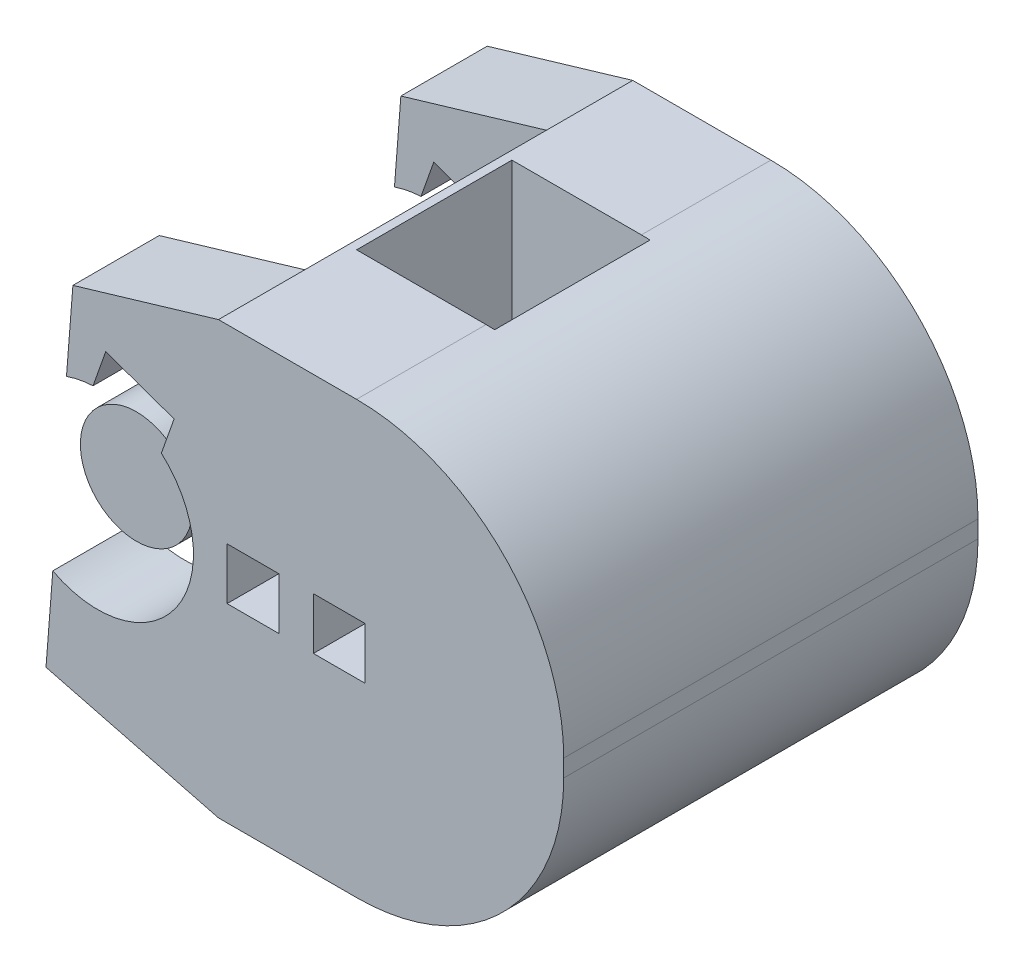
SolidWorks part; units mm, degrees
material "ABS"
ref_plane "正面" through (0, 0, 0) normal (0, 0, 1) x (1, 0, 0)
ref_plane "平面" through (0, 0, 0) normal (0, 1, 0) x (1, 0, 0)
ref_plane "右側面" through (0, 0, 0) normal (1, 0, 0) x (0, 0, -1)
sketch "ｽｹｯﾁ1" plane through (0, 0, 0) normal (0, 0, 1) x (1, 0, 0)
  circle A0 centre (0, 0) radius 3.25
  dimension "D1" = 6.5
extrude "ﾎﾞｽ - 押し出し1" add sketch "ｽｹｯﾁ1" along normal blind 19.5
ref_plane "平面1" through (5, 0, 0) normal (1, 0, 0) x (0, 0, -1)
sketch "ｽｹｯﾁ2" plane through (5, 0, 0) normal (1, 0, 0) x (0, 0, -1)
  line L0 (-19.5, 0) -> (0, 0) construction
  line L1 (-19.5, 3.25) -> (-19.5, -3.25) construction
  line L3 (-2.75, -7.5) -> (-16.75, -7.5)
  line L4 (-2.75, -7.5) -> (-2.75, 7.5)
  line L5 (-2.75, 7.5) -> (-16.75, 7.5)
  line L6 (-16.75, -7.5) -> (-16.75, 7.5)
  line L7 (-2.75, -7.5) -> (-16.75, 7.5) construction
  line L8 (-2.75, 7.5) -> (-16.75, -7.5) construction
  point P5 (-9.75, 0)
  dimension "D1" = 15
  dimension "D2" = 14
extrude "ﾎﾞｽ - 押し出し2" add sketch "ｽｹｯﾁ2" along normal blind 2 separate body
sketch "ｽｹｯﾁ3" plane through (0, 0, 2.75) normal (0, 0, -1) x (-1, 0, 0)
  line L0 (0, 0) -> (-5, 4.5)
  line L1 (-5, 3.575) -> (-5, -3.575) construction
  line L2 (-5, 4.5) -> (-5, -4.5)
  line L3 (-5, -4.5) -> (0, 0)
  dimension "D1" = 9
extrude "ﾎﾞｽ - 押し出し3" add sketch "ｽｹｯﾁ3" against normal up to surface (14 mm away) up to face at (6, 0, 16.75)
fillet "ﾌｨﾚｯﾄ1" radius 2 4 edges at (5, -4.5, 9.75) (2.4157, -2.1741, 9.75) (2.4157, 2.1741, 9.75) (5, 4.5, 9.75)
sketch "ｽｹｯﾁ5" plane through (7, 0, 0) normal (1, 0, 0) x (0, 0, -1)
  line L0 (-16.75, 0) -> (-2.75, 0) construction
  line L3 (-16.75, 7.5) -> (-16.75, -7.5) construction
  line L16 (-2.75, -2.9305) -> (-2.75, 2.9305) construction
  line L18 (-21.75, -12.5) -> (2.25, -12.5)
  line L19 (-21.75, -12.5) -> (-21.75, 12.5)
  line L20 (-21.75, 12.5) -> (2.25, 12.5)
  line L21 (2.25, -12.5) -> (2.25, 12.5)
  line L22 (-21.75, -12.5) -> (2.25, 12.5) construction
  line L23 (-21.75, 12.5) -> (2.25, -12.5) construction
  point P6 (-9.75, 0)
  dimension "D1" = 25
  dimension "D2" = 24
extrude "ﾎﾞｽ - 押し出し4" add sketch "ｽｹｯﾁ5" along normal blind 20
sketch "ｽｹｯﾁ6" plane through (27, 0, 0) normal (1, 0, 0) x (0, 0, -1)
  line L0 (-21.75, 0) -> (2.25, 0) construction
  line L1 (-21.75, 12.5) -> (-21.75, -12.5) construction
  line L2 (2.25, -12.5) -> (2.25, 12.5) construction
  line L4 (-11.75, -1.25) -> (-14.25, -1.25)
  line L5 (-11.75, -1.25) -> (-11.75, 1.25)
  line L6 (-11.75, 1.25) -> (-14.25, 1.25)
  line L7 (-14.25, -1.25) -> (-14.25, 1.25)
  line L8 (-11.75, -1.25) -> (-14.25, 1.25) construction
  line L9 (-11.75, 1.25) -> (-14.25, -1.25) construction
  line L10 (-5.25, -1.25) -> (-7.75, -1.25)
  line L11 (-5.25, -1.25) -> (-5.25, 1.25)
  line L12 (-5.25, 1.25) -> (-7.75, 1.25)
  line L13 (-7.75, -1.25) -> (-7.75, 1.25)
  line L14 (-5.25, -1.25) -> (-7.75, 1.25) construction
  line L15 (-5.25, 1.25) -> (-7.75, -1.25) construction
  point P6 (-13, 0)
  point P8 (-9.75, 0)
  point P12 (-6.5, 0)
  dimension "D1" = 3.25
  dimension "D2" = 3.25
  dimension "D3" = 2.5
  dimension "D4" = 2.5
extrude "ｶｯﾄ - 押し出し1" cut sketch "ｽｹｯﾁ6" against normal through all
sketch "ｽｹｯﾁ7" plane through (0, 0, 21.75) normal (0, 0, 1) x (1, 0, 0)
  line L0 (0, 0) -> (27, 0) construction
  line L1 (27, 12.5) -> (27, -12.5) construction
  line L2 (7, 12.5) -> (7, -12.5) construction
  line L3 (10.5, 1.5) -> (7.5, 1.5)
  line L4 (10.5, 1.5) -> (10.5, -1.5)
  line L5 (10.5, -1.5) -> (7.5, -1.5)
  line L6 (7.5, 1.5) -> (7.5, -1.5)
  line L7 (10.5, 1.5) -> (7.5, -1.5) construction
  line L8 (10.5, -1.5) -> (7.5, 1.5) construction
  line L9 (15.5, 1.5) -> (12.5, 1.5)
  line L10 (15.5, 1.5) -> (15.5, -1.5)
  line L11 (15.5, -1.5) -> (12.5, -1.5)
  line L12 (12.5, 1.5) -> (12.5, -1.5)
  line L13 (15.5, 1.5) -> (12.5, -1.5) construction
  line L14 (15.5, -1.5) -> (12.5, 1.5) construction
  point P5 (9, 0)
  point P10 (14, 0)
  dimension "D1" = 3
  dimension "D2" = 2
  dimension "D3" = 5
extrude "ｶｯﾄ - 押し出し2" cut sketch "ｽｹｯﾁ7" against normal through all
sketch "ｽｹｯﾁ8" plane through (0, 12.5, 0) normal (0, 1, 0) x (1, 0, 0)
  line L0 (3, -5.25) -> (7.5, -5.25) construction
  line L1 (7.5, -5.25) -> (15.5, -5.25)
  line L2 (7.5, -5.25) -> (7.5, -14.25)
  line L3 (7.5, -14.25) -> (15.5, -14.25)
  line L4 (15.5, -5.25) -> (15.5, -14.25)
  line L5 (-3, -14.25) -> (7.5, -14.25) construction
  line L6 (7.5, 2.25) -> (7.5, -21.75) construction
  line L7 (15.5, 2.25) -> (15.5, -5.25) construction
extrude "ｶｯﾄ - 押し出し3" cut sketch "ｽｹｯﾁ8" against normal through all
sketch "ｽｹｯﾁ9" plane through (15.5, 0, 0) normal (-1, 0, 0) x (0, 0, 1)
  line L4 (11.75, -1.25) -> (14.25, -1.25)
  line L5 (14.25, -1.25) -> (14.25, 1.25)
  line L6 (14.25, 1.25) -> (11.75, 1.25)
  line L7 (11.75, 1.25) -> (11.75, -1.25)
  line L8 (11.75, -1.25) -> (14.25, -1.25)
  line L9 (14.25, -1.25) -> (14.25, 1.25)
  line L10 (14.25, 1.25) -> (11.75, 1.25)
  line L11 (11.75, 1.25) -> (11.75, -1.25)
  line L12 (5.25, -1.25) -> (7.75, -1.25)
  line L13 (5.25, 1.25) -> (5.25, -1.25)
  line L14 (7.75, 1.25) -> (5.25, 1.25)
  line L15 (7.75, -1.25) -> (7.75, 1.25)
  line L16 (5.25, -1.25) -> (7.75, -1.25)
  line L17 (5.25, 1.25) -> (5.25, -1.25)
  line L18 (7.75, 1.25) -> (5.25, 1.25)
  line L19 (7.75, -1.25) -> (7.75, 1.25)
  dimension "D1" = 0
  dimension "D2" = 0
extrude "ﾎﾞｽ - 押し出し5" add sketch "ｽｹｯﾁ9" against normal up to surface (11.5 mm away) up to face at (27, 0, 13)
fillet "ﾌｨﾚｯﾄ7" radius 12 2 edges at (27, -12.5, 9.75) (27, 12.5, 9.75)
sketch "ｽｹｯﾁ10" plane through (0, 0, 2.75) normal (0, 0, -1) x (-1, 0, 0)
  line L3 (1.8051, 5.2483) -> (2.5982, -4.9043) construction
  line L4 (1.8051, 5.2483) -> (1.4339, 10)
  line L5 (1.4339, 10) -> (-7, 12.5)
  line L6 (-4.4294, 6.23) -> (-3.692, 4.1438)
  line L7 (-0.4695, 7.6297) -> (-4.4294, 6.23)
  line L8 (0.2679, 5.5435) -> (-0.4695, 7.6297)
  line L9 (-4.4294, 6.23) -> (-3.692, 4.1438)
  line L10 (-0.4695, 7.6297) -> (-4.4294, 6.23)
  line L11 (0.2679, 5.5435) -> (-0.4695, 7.6297)
  line L12 (2.5982, -4.9043) -> (2.9915, -9.9393)
  line L13 (2.9915, -9.9393) -> (-7, -12.5)
  line L14 (1.4339, 10) -> (-7, 10) construction
  line L15 (-7, -12.5) -> (-7, 12.5) construction
  line L16 (2.9915, -9.9393) -> (-7, -9.9393) construction
  line L17 (-7, 12.5) -> (-7, -12.5)
  arc A4 (1.8051, 5.2483) -> (0.2679, 5.5435) centre (0, 0) ccw
  arc A5 (-3.692, 4.1438) -> (2.5982, -4.9043) centre (0, 0) ccw
  arc A6 (1.8051, 5.2483) -> (0.2679, 5.5435) centre (0, 0) ccw
  arc A7 (-3.692, 4.1438) -> (2.5982, -4.9043) centre (0, 0) ccw
  point P0 (2.9652, -9.6768)
  dimension "D2" = 20
  dimension "D3" = 2.5
  dimension "D1" = 0.1
extrude "ﾎﾞｽ - 押し出し6" add sketch "ｽｹｯﾁ10" along normal up to surface (5 mm away) up to face at (9, 0, -2.25)
sketch "ｽｹｯﾁ11" plane through (0, 0, 16.75) normal (0, 0, -1) x (-1, 0, 0)
  line L8 (1.8051, 5.2483) -> (1.4339, 10)
  line L9 (1.4339, 10) -> (-7, 12.5)
  line L10 (-7, 12.5) -> (-7, -12.5)
  line L11 (-7, -12.5) -> (2.9915, -9.9393)
  line L12 (2.9915, -9.9393) -> (2.5982, -4.9043)
  line L13 (-3.692, 4.1438) -> (-4.4294, 6.23)
  line L14 (-4.4294, 6.23) -> (-0.4695, 7.6297)
  line L15 (-0.4695, 7.6297) -> (0.2679, 5.5435)
  line L16 (1.8051, 5.2483) -> (1.4339, 10)
  line L17 (1.4339, 10) -> (-7, 12.5)
  line L18 (-7, 12.5) -> (-7, -12.5)
  line L19 (-7, -12.5) -> (2.9915, -9.9393)
  line L20 (2.9915, -9.9393) -> (2.5982, -4.9043)
  line L21 (-3.692, 4.1438) -> (-4.4294, 6.23)
  line L22 (-4.4294, 6.23) -> (-0.4695, 7.6297)
  line L23 (-0.4695, 7.6297) -> (0.2679, 5.5435)
  arc A2 (-3.692, 4.1438) -> (2.5982, -4.9043) centre (0, 0) ccw
  arc A3 (1.8051, 5.2483) -> (0.2679, 5.5435) centre (0, 0) ccw
  arc A4 (-3.692, 4.1438) -> (2.5982, -4.9043) centre (0, 0) ccw
  arc A5 (1.8051, 5.2483) -> (0.2679, 5.5435) centre (0, 0) ccw
  dimension "D1" = 0
extrude "ﾎﾞｽ - 押し出し7" add sketch "ｽｹｯﾁ11" against normal up to surface (5 mm away) up to face at (9, 0, 21.75)
equation "\"D2@ｽｹｯﾁ6\"=\"D1@ｽｹｯﾁ6\""
